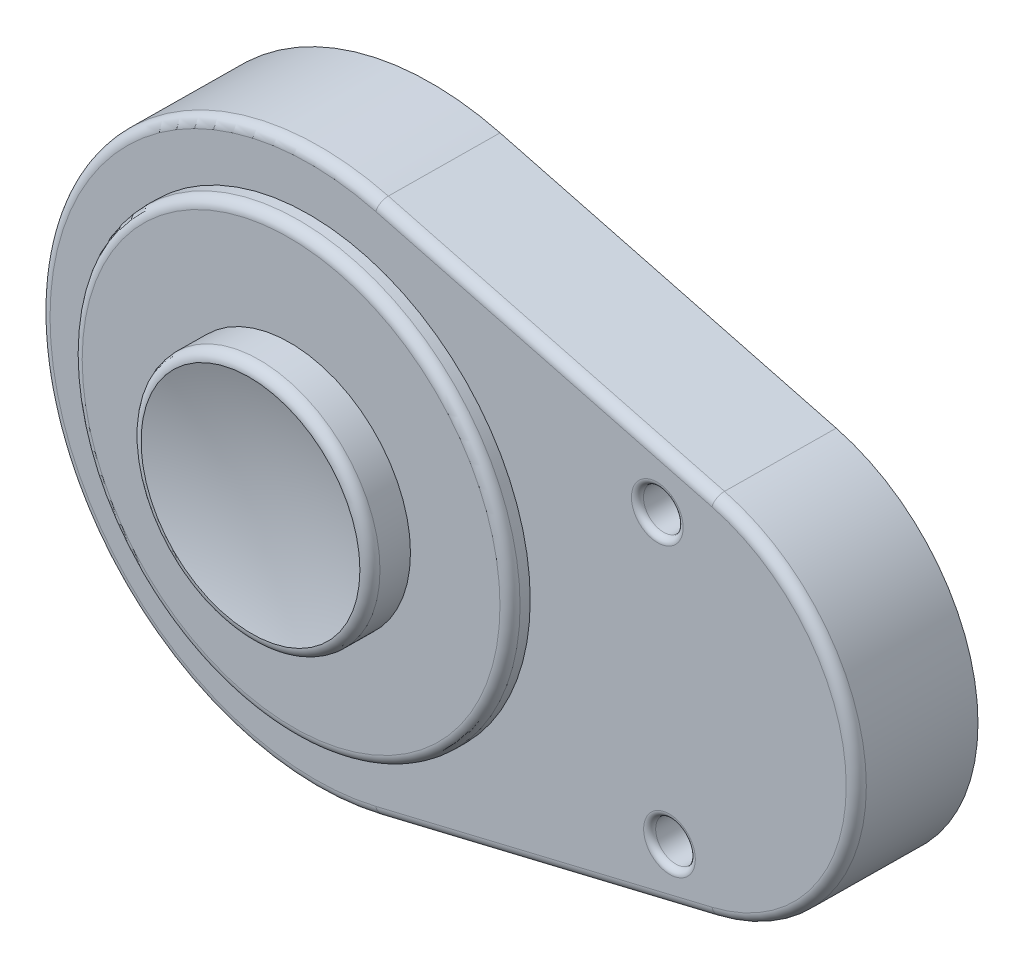
SolidWorks part; units mm, degrees
ref_plane "Front Plane" through (0, 0, 0) normal (0, 0, 1) x (1, 0, 0)
ref_plane "Top Plane" through (0, 0, 0) normal (0, 1, 0) x (1, 0, 0)
ref_plane "Right Plane" through (0, 0, 0) normal (1, 0, 0) x (0, 0, -1)
sketch "Sketch1" plane through (-0.6093, 0, 59.9969) normal (-0.0102, 0, 0.9999) x (0.9999, 0.0053, 0.0102)
  line L2 (13.0923, 339.4793) -> (-71.2833, 360.8712)
  line L6 (13.0923, 339.4793) -> (-71.2833, 360.8712)
  line L7 (-71.9893, 227.8977) -> (12.6087, 248.3925)
  line L8 (-71.9893, 227.8977) -> (12.6087, 248.3925)
  arc A2 (-71.2833, 360.8712) -> (-71.9893, 227.8977) centre (-88.1176, 294.472) ccw
  arc A6 (-71.2833, 360.8712) -> (-71.9893, 227.8977) centre (-88.1176, 294.472) ccw
  arc A7 (12.6087, 248.3925) -> (13.0923, 339.4793) centre (1.5609, 293.9959) ccw
  arc A8 (12.6087, 248.3925) -> (13.0923, 339.4793) centre (1.5609, 293.9959) ccw
  dimension "D1" = 0
extrude "Boss-Extrude1" add sketch "Sketch1" along normal blind 30
sketch "Sketch2" plane through (-0.9139, 0, 89.9954) normal (-0.0102, 0, 0.9999) x (0.9999, 0.0053, 0.0102)
  circle A0 centre (-88.4332, 294.4736) radius 55
  dimension "D1" = 110
extrude "Boss-Extrude2" add sketch "Sketch2" along normal blind 5
sketch "Sketch3" plane through (-0.9647, 0, 94.9951) normal (-0.0102, 0, 0.9999) x (0.9999, 0.0053, 0.0102)
  circle A0 centre (-88.4332, 294.4736) radius 30
  dimension "D1" = 60
extrude "Boss-Extrude3" add sketch "Sketch3" along normal blind 10
sketch "Sketch4" plane through (-0.9139, 0, 89.9954) normal (-0.0102, 0, 0.9999) x (0.9999, 0.0053, 0.0102)
  line L0 (0.9822, 184.9974) -> (1.5609, 293.9959) construction
  line L1 (1.5609, 293.9959) -> (-88.4332, 294.4736) construction
  circle A0 centre (-1.3183, 329.0116) radius 5
  circle A1 centre (1.3754, 259.0635) radius 5
  dimension "D1" = 10
  dimension "D2" = 10
  dimension "D3" = 70
  dimension "D4" = 35
extrude "Cut-Extrude4" cut sketch "Sketch4" against normal blind 20
sketch "Sketch5" plane through (-0.9139, 0, 89.9954) normal (-0.0102, 0, 0.9999) x (0.9999, 0.0053, 0.0102)
  circle A0 centre (-1.3183, 329.0116) radius 3
  circle A1 centre (1.3754, 259.0635) radius 3
extrude "Cut-Extrude5" cut sketch "Sketch5" against normal through all
fillet "Fillet1" radius 2.5 6 edges at (46.0062, 294, 90.4718) (-31.8665, 237.9841, 89.681) (-159.0855, 294, 88.3891) (-35.9582, 294, 94.6397) (-61.0585, 294, 104.3854) (-31.8665, 350.0159, 89.681)
fillet "Fillet2" radius 1.5 2 edges at (4.0858, 259.0671, 90.0461) (1.021, 329, 90.015)
dome "Dome1" faces to dome 1 distance 4 reverse direction yes elliptical dome no face at (-63.5584, 294, 104.36) parameters "D1"=4
